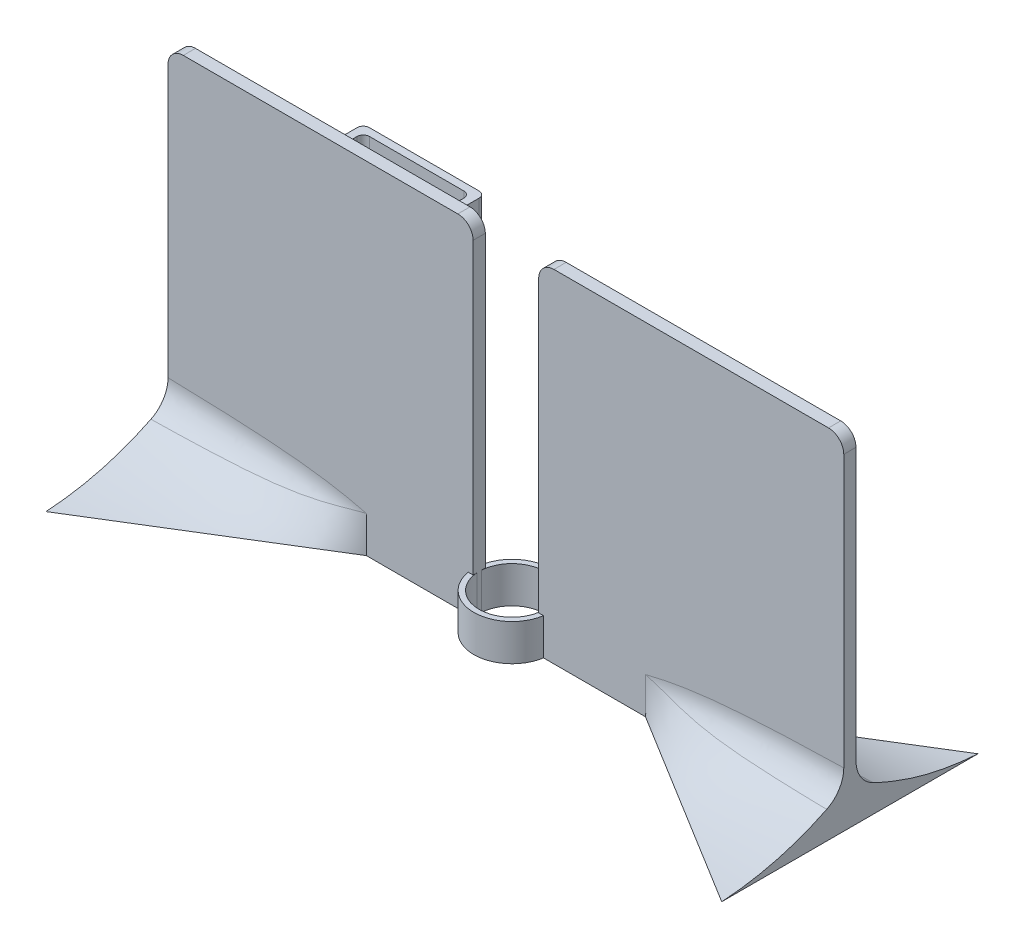
SolidWorks part; units mm, degrees
ref_plane "Front Plane" through (0, 0, 0) normal (0, 0, 1) x (1, 0, 0)
ref_plane "Top Plane" through (0, 0, 0) normal (0, 1, 0) x (1, 0, 0)
ref_plane "Right Plane" through (0, 0, 0) normal (1, 0, 0) x (0, 0, -1)
ref_plane "Plane1" through (10.75, 0, 0) normal (1, 0, 0) x (0, 0, -1)
ref_plane "Plane2" through (120, 0, 0) normal (1, 0, 0) x (0, 0, -1)
sketch "Sketch1" plane through (10.75, 0, 0) normal (1, 0, 0) x (0, 0, -1)
  line L0 (0, 0) -> (0, 12)
  line L1 (0, 55) -> (0, -55) construction
  line L2 (0, 12) -> (0, 112)
  line L3 (0, 112) -> (2, 112)
  line L4 (0, 112) -> (-2, 112)
  line L6 (2, 112) -> (-2, 112)
  line L7 (2, 112) -> (2, 12)
  line L8 (2, 12) -> (-2, 12)
  line L9 (-2, 112) -> (-2, 12)
  line L10 (2, 12) -> (-2, 12)
  line L11 (2, 12) -> (2, 0)
  line L12 (2, 0) -> (-2, 0)
  line L13 (-2, 12) -> (-2, 0)
  dimension "D1" = 100
  dimension "D2" = 4
  dimension "D3" = 12
extrude "Boss-Extrude1" add sketch "Sketch1" along normal blind 100 contours L7 L6 L9 L8
sketch "Sketch5" plane through (110.75, 0, 0) normal (1, 0, 0) x (0, 0, -1)
  line L0 (2, 112) -> (2, 12) construction
  line L1 (-2, 12) -> (2, 12)
  line L6 (-42, 0) -> (42, 0)
  spline S0 degree 2 poles (-2, 12) (-20.5349, 1.3112) (-42, 0) knots 0 0 0 1 1 1
  spline S1 degree 2 poles (2, 12) (20.5349, 1.3112) (42, 0) knots 0 0 0 1 1 1
  dimension "D2" = 4
  dimension "D3" = 40
  dimension "D1" = 40
sketch "Sketch6" plane through (10.75, 0, 0) normal (-1, 0, 0) x (0, 0, 1)
  line L3 (-2, 12) -> (2, 12)
  line L4 (-2, 12) -> (-2, 0)
  line L5 (-2, 0) -> (2, 0)
  line L6 (2, 12) -> (2, 0)
  dimension "D1" = 12
ref_plane "Plane3" through (45.75, 0, 0) normal (1, 0, 0) x (0, 0, -1)
sketch "Sketch7" plane through (45.75, 0, 0) normal (1, 0, 0) x (0, 0, -1)
  line L1 (-2, 12) -> (2, 12)
  line L2 (-2, 12) -> (-2, 0)
  line L3 (-2, 0) -> (2, 0)
  line L4 (2, 12) -> (2, 0)
extrude "Boss-Extrude2" add sketch "Sketch6" against normal up to vertex (35 mm away) contours L6 L5 L4 L3 up to point (45.75, 0, -2)
loft "Loft3" add profiles "Sketch7", "Sketch5" connector at (45.75, 0, -2) connector at (110.75, 0, -42)
mirror "Mirror3" about plane through (0, 0, 0) normal (1, 0, 0) of bodies 105
sketch "Sketch14" plane through (0, 0, 0) normal (0, 1, 0) x (1, 0, 0)
  circle A0 centre (0, 0) radius 10.775
  circle A1 centre (0, 0) radius 12.5
  dimension "D1" = 21.55
  dimension "D2" = 25
extrude "Boss-Extrude3" add sketch "Sketch14" along normal blind 12
sketch "Sketch15" plane through (0, 0, -2) normal (0, 0, -1) x (-1, 0, 0)
  line L0 (110.75, 112) -> (110.75, 12) construction
  line L1 (50.75, 78) -> (90.75, 78)
  line L2 (50.75, 78) -> (50.75, 28)
  line L3 (50.75, 28) -> (90.75, 28)
  line L4 (90.75, 78) -> (90.75, 28)
  line L5 (110.75, 112) -> (10.75, 112) construction
  dimension "D1" = 20
  dimension "D2" = 40
  dimension "D3" = 34
  dimension "D4" = 50
extrude "Boss-Extrude4" add sketch "Sketch15" along normal blind 40
sketch "Sketch16" plane through (0, 78, 0) normal (0, 1, 0) x (1, 0, 0)
  line L0 (-90.75, 2) -> (-50.75, 2) construction
  line L1 (-53.25, 2) -> (-88.25, 2)
  line L2 (-53.25, 2) -> (-53.25, 39.5)
  line L3 (-53.25, 39.5) -> (-88.25, 39.5)
  line L4 (-88.25, 2) -> (-88.25, 39.5)
  line L5 (-50.75, 42) -> (-50.75, 2) construction
  line L6 (-90.75, 42) -> (-90.75, 2) construction
  dimension "D1" = 37.5
  dimension "D2" = 2.5
  dimension "D3" = 2.5
extrude "Cut-Extrude1" cut sketch "Sketch16" against normal blind 47.5
fillet "Fillet1" radius 10 4 edges
fillet "Fillet2" radius 5 4 edges at (110.75, 112, 0) (-10.75, 112, 0) (10.75, 112, 0) (-110.75, 112, 0)
fillet "Fillet3" radius 2 16 edges at (-50.75, 53, -2) (-90.75, 53, -2) (-70.75, 30.5, -2) (-88.25, 30.5, -20.75) (-70.75, 30.5, -39.5) (-53.25, 30.5, -20.75) (-50.75, 28, -22) (-70.75, 28, -42) (-90.75, 28, -22) (-70.75, 28, -2) (-53.25, 54.25, -2) (-88.25, 54.25, -2) (-88.25, 54.25, -39.5) (-53.25, 54.25, -39.5) (-50.75, 53, -42) (-90.75, 53, -42)
equation "\"D1@Sketch5\"=\"D3@Sketch5\""
